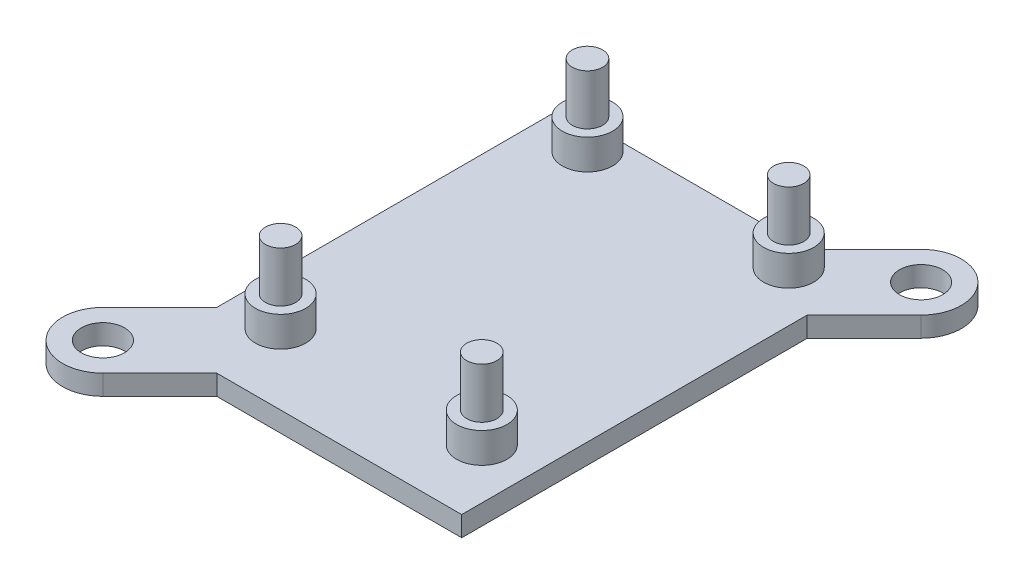
SolidWorks part; units mm, degrees
ref_plane "Front Plane" through (0, 0, 0) normal (0, 0, 1) x (1, 0, 0)
ref_plane "Top Plane" through (0, 0, 0) normal (0, 1, 0) x (1, 0, 0)
ref_plane "Right Plane" through (0, 0, 0) normal (1, 0, 0) x (0, 0, -1)
sketch "Sketch1" plane through (0, 0, 0) normal (0, 1, 0) x (1, 0, 0)
  line L0 (0, 0) -> (30, 0)
  line L1 (30, 0) -> (30, -40)
  line L2 (30, -40) -> (0, -40)
  line L3 (0, -40) -> (0, 0)
  line L4 (30, 0) -> (35.6569, 5.6569) construction
  line L5 (32.8284, 2.8284) -> (35.6569, 0) construction
  line L6 (32.8284, 2.8284) -> (30, 5.6569) construction
  line L7 (35.6569, 0) -> (30, -5.6569)
  line L8 (30, -5.6569) -> (30, 0)
  line L9 (30, 5.6569) -> (24.3431, 0)
  line L10 (24.3431, 0) -> (30, -5.6569)
  line L11 (0, -40) -> (-5.6569, -45.6569) construction
  line L12 (-2.8284, -42.8284) -> (0, -45.6569) construction
  line L13 (-2.8284, -42.8284) -> (-5.6569, -40) construction
  line L14 (-5.6569, -40) -> (0, -34.3431)
  line L15 (0, -45.6569) -> (5.6569, -40)
  line L16 (5.6569, -40) -> (0, -34.3431)
  circle A0 centre (32.8284, 2.8284) radius 2.15
  arc A1 (30, 5.6569) -> (35.6569, 0) centre (32.8284, 2.8284) cw
  circle A2 centre (-2.8284, -42.8284) radius 2.15
  arc A3 (-5.6569, -40) -> (0, -45.6569) centre (-2.8284, -42.8284) ccw
  dimension "D4" = 4.3
  dimension "D8" = 4.3
  dimension "D1" = 30
  dimension "D2" = 40
  dimension "D3" = 8
  dimension "D5" = 4
  dimension "D6" = 4
  dimension "D7" = 8
  dimension "D9" = 4
extrude "Boss-Extrude1" add sketch "Sketch1" along normal blind 2 contours L10 L0 L3 L2 L1 | A1 L9 L0 L1 L7 A0 | L0 L10 L1 | L14 A3 L15 L2 L3 A2 | L2 L16 L3 region at (15, 0, 20) region at (27.2964, 0, -2.7036) region at (28.1144, 0, 1.8856) region at (1.8856, 0, 38.1144) region at (-0.1766, 0, 37.1716)
sketch "Sketch2" plane through (0, 0, 0) normal (0, 1, 0) x (1, 0, 0)
  line L0 (15, 0) -> (15, -40) construction
  line L3 (15, -2.5) -> (25, -2.5) construction
  line L4 (25, -2.5) -> (25, -33) construction
  line L5 (15, -2.5) -> (5, -2.5) construction
  line L6 (5, -2.5) -> (5, -33) construction
  line L7 (0, 0) -> (24.3431, 0) construction
  circle A0 centre (25, -2.5) radius 1.5
  circle A1 centre (25, -33) radius 1.5
  circle A2 centre (5, -33) radius 1.5
  circle A3 centre (5, -2.5) radius 1.5
  dimension "D2" = 3
  dimension "D5" = 3
  dimension "D6" = 3
  dimension "D7" = 3
  dimension "D1" = 10
  dimension "D3" = 2.5
  dimension "D4" = 30.5
  dimension "D8" = 30.5
  dimension "D9" = 2.5
  dimension "D10" = 10
extrude "Boss-Extrude2" add sketch "Sketch2" along normal blind 10 contours A3 | A2 | A1 | A0
sketch "Sketch3" plane through (0, 0, 0) normal (0, 1, 0) x (1, 0, 0)
  circle A0 centre (5, -2.5) radius 2.5
  circle A1 centre (25, -2.5) radius 2.5
  circle A2 centre (25, -33) radius 2.5
  circle A4 centre (5, -33) radius 2.5
  dimension "D1" = 5
  dimension "D2" = 5
extrude "Boss-Extrude3" add sketch "Sketch3" along normal blind 5
